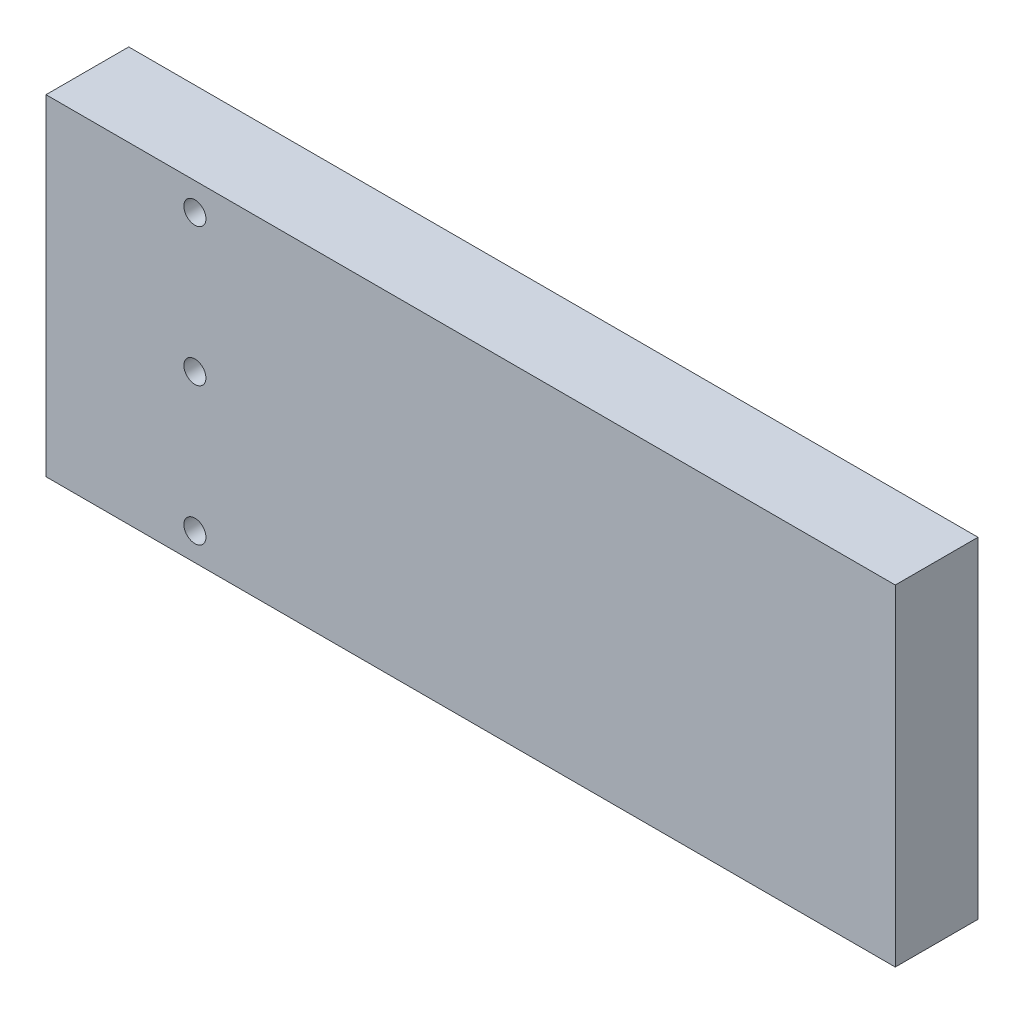
SolidWorks part; units mm, degrees
ref_plane "Plan de face" through (0, 0, 0) normal (0, 0, 1) x (1, 0, 0)
ref_plane "Plan de dessus" through (0, 0, 0) normal (0, 1, 0) x (1, 0, 0)
ref_plane "Plan de droite" through (0, 0, 0) normal (1, 0, 0) x (0, 0, -1)
sketch "Esquisse1" plane through (0, 0, 0) normal (0, 0, 1) x (1, 0, 0)
  line L1 (0, 0) -> (54, 0)
  line L2 (0, 0) -> (0, -60)
  line L3 (0, -60) -> (54, -60)
  line L4 (54, 0) -> (54, -60)
  line L5 (54, 0) -> (100, 0)
  line L6 (54, 0) -> (54, -60)
  line L7 (54, -60) -> (100, -60)
  line L8 (100, 0) -> (100, -60)
  line L9 (100, -60) -> (154, -60)
  line L10 (100, -60) -> (100, 0)
  line L11 (100, 0) -> (154, 0)
  line L12 (154, -60) -> (154, 0)
  circle A0 centre (27, -55) radius 2
  circle A1 centre (27, -30) radius 2
  circle A2 centre (27, -5) radius 2
  point P11 (27, 0)
  dimension "D1" = 4
  dimension "D2" = 4
  dimension "D3" = 4
  dimension "D4" = 60
  dimension "D5" = 54
  dimension "D6" = 0
  dimension "D7" = 0
  dimension "D8" = 0
  dimension "D9" = 30
  dimension "D10" = 5
  dimension "D11" = 5
  dimension "D12" = 54
  dimension "D13" = 100
extrude "Boss.-Extru.1" add sketch "Esquisse1" along normal blind 15 contours L4 L1 L2 L3 A2 A1 A0 | L8 L5 L4 L7 | L9 L12 L11 L8 region at (27, -0.8072, 0) region at (77, -30, 0) region at (127, -30, 0)
